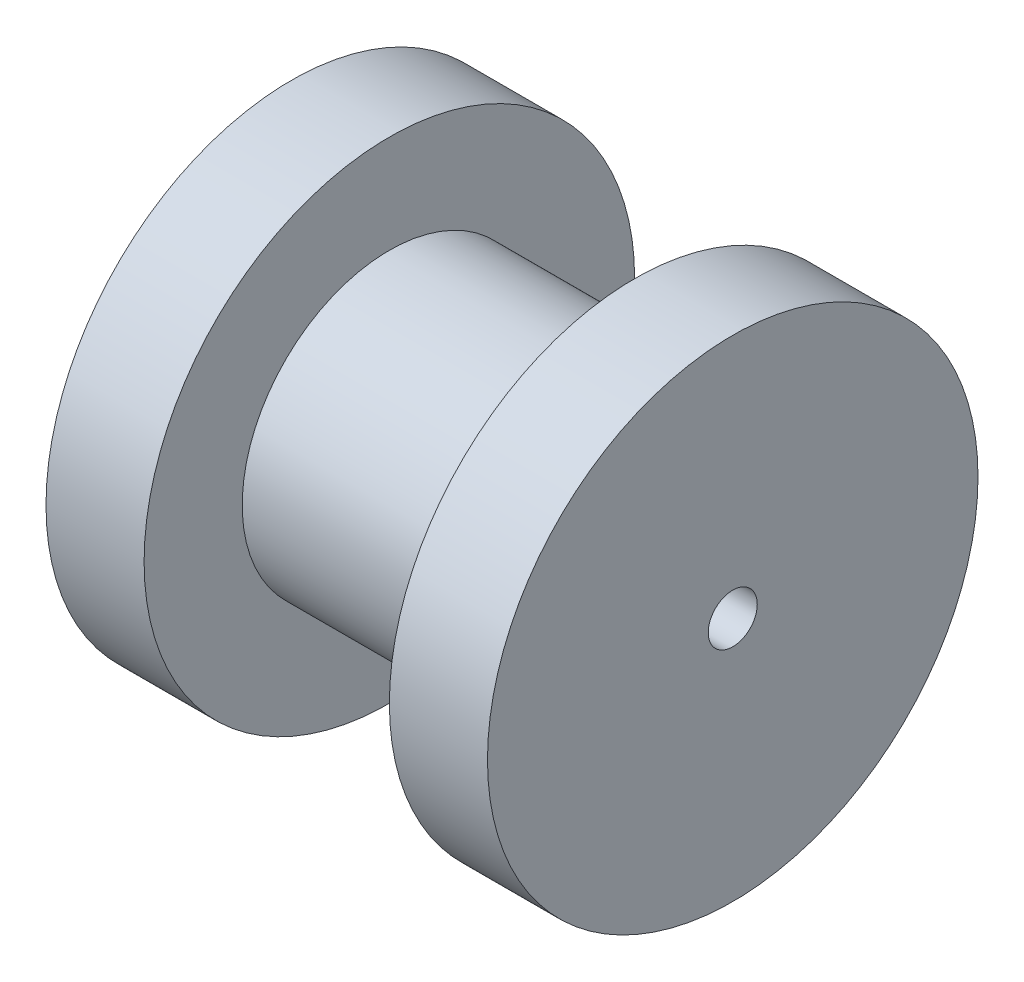
SolidWorks part; units mm, degrees
ref_plane "Front Plane" through (0, 0, 0) normal (0, 0, 1) x (1, 0, 0)
ref_plane "Top Plane" through (0, 0, 0) normal (0, 1, 0) x (1, 0, 0)
ref_plane "Right Plane" through (0, 0, 0) normal (1, 0, 0) x (0, 0, -1)
sketch "Sketch1" plane through (0, 0, 0) normal (1, 0, 0) x (0, 0, -1)
  circle A0 centre (0, 0) radius 5
extrude "Boss-Extrude1" add sketch "Sketch1" along normal blind 2
sketch "Sketch2" plane through (2, 0, 0) normal (1, 0, 0) x (0, 0, -1)
  circle A0 centre (0, 0) radius 3
extrude "Boss-Extrude2" add sketch "Sketch2" along normal blind 5
sketch "Sketch5" plane through (7, 0, 0) normal (1, 0, 0) x (0, 0, -1)
  circle A0 centre (0, 0) radius 5
extrude "Boss-Extrude4" add sketch "Sketch5" along normal blind 2
sketch "Sketch6" plane through (0, 0, 0) normal (-1, 0, 0) x (0, 0, 1)
  line L0 (0, 0) -> (0, 2.2) construction
  line L1 (0.096, 2.1979) -> (0.109, 2.4976)
  line L2 (-0.096, 2.1979) -> (-0.109, 2.4976)
  line L3 (0.4762, 2.1479) -> (0.5411, 2.4407)
  line L4 (0.2872, 2.1812) -> (0.3263, 2.4786)
  line L5 (0.8419, 2.0325) -> (0.9567, 2.3097)
  line L6 (0.6616, 2.0982) -> (0.7518, 2.3843)
  line L7 (1.1821, 1.8555) -> (1.3432, 2.1085)
  line L8 (1.0158, 1.9514) -> (1.1544, 2.2175)
  line L9 (1.4863, 1.622) -> (1.689, 1.8432)
  line L10 (1.3393, 1.7454) -> (1.5219, 1.9834)
  line L11 (1.7454, 1.3393) -> (1.9834, 1.5219)
  line L12 (1.622, 1.4863) -> (1.8432, 1.689)
  line L13 (1.9514, 1.0158) -> (2.2175, 1.1544)
  line L14 (1.8555, 1.1821) -> (2.1085, 1.3432)
  line L15 (2.0982, 0.6616) -> (2.3843, 0.7518)
  line L16 (2.0325, 0.8419) -> (2.3097, 0.9567)
  line L17 (2.1812, 0.2872) -> (2.4786, 0.3263)
  line L18 (2.1479, 0.4762) -> (2.4407, 0.5411)
  line L19 (2.1979, -0.096) -> (2.4976, -0.109)
  line L20 (2.1979, 0.096) -> (2.4976, 0.109)
  line L21 (2.1479, -0.4762) -> (2.4407, -0.5411)
  line L22 (2.1812, -0.2872) -> (2.4786, -0.3263)
  line L23 (2.0325, -0.8419) -> (2.3097, -0.9567)
  line L24 (2.0982, -0.6616) -> (2.3843, -0.7518)
  line L25 (1.8555, -1.1821) -> (2.1085, -1.3432)
  line L26 (1.9514, -1.0158) -> (2.2175, -1.1544)
  line L27 (1.622, -1.4863) -> (1.8432, -1.689)
  line L28 (1.7454, -1.3393) -> (1.9834, -1.5219)
  line L29 (1.3393, -1.7454) -> (1.5219, -1.9834)
  line L30 (1.4863, -1.622) -> (1.689, -1.8432)
  line L31 (1.0158, -1.9514) -> (1.1544, -2.2175)
  line L32 (1.1821, -1.8555) -> (1.3432, -2.1085)
  line L33 (0.6616, -2.0982) -> (0.7518, -2.3843)
  line L34 (0.8419, -2.0325) -> (0.9567, -2.3097)
  line L35 (0.2872, -2.1812) -> (0.3263, -2.4786)
  line L36 (0.4762, -2.1479) -> (0.5411, -2.4407)
  line L37 (-0.096, -2.1979) -> (-0.109, -2.4976)
  line L38 (0.096, -2.1979) -> (0.109, -2.4976)
  line L39 (-0.4762, -2.1479) -> (-0.5411, -2.4407)
  line L40 (-0.2872, -2.1812) -> (-0.3263, -2.4786)
  line L41 (-0.8419, -2.0325) -> (-0.9567, -2.3097)
  line L42 (-0.6616, -2.0982) -> (-0.7518, -2.3843)
  line L43 (-1.1821, -1.8555) -> (-1.3432, -2.1085)
  line L44 (-1.0158, -1.9514) -> (-1.1544, -2.2175)
  line L45 (-1.4863, -1.622) -> (-1.689, -1.8432)
  line L46 (-1.3393, -1.7454) -> (-1.5219, -1.9834)
  line L47 (-1.7454, -1.3393) -> (-1.9834, -1.5219)
  line L48 (-1.622, -1.4863) -> (-1.8432, -1.689)
  line L49 (-1.9514, -1.0158) -> (-2.2175, -1.1544)
  line L50 (-1.8555, -1.1821) -> (-2.1085, -1.3432)
  line L51 (-2.0982, -0.6616) -> (-2.3843, -0.7518)
  line L52 (-2.0325, -0.8419) -> (-2.3097, -0.9567)
  line L53 (-2.1812, -0.2872) -> (-2.4786, -0.3263)
  line L54 (-2.1479, -0.4762) -> (-2.4407, -0.5411)
  line L55 (-2.1979, 0.096) -> (-2.4976, 0.109)
  line L56 (-2.1979, -0.096) -> (-2.4976, -0.109)
  line L57 (-2.1479, 0.4762) -> (-2.4407, 0.5411)
  line L58 (-2.1812, 0.2872) -> (-2.4786, 0.3263)
  line L59 (-2.0325, 0.8419) -> (-2.3097, 0.9567)
  line L60 (-2.0982, 0.6616) -> (-2.3843, 0.7518)
  line L61 (-1.8555, 1.1821) -> (-2.1085, 1.3432)
  line L62 (-1.9514, 1.0158) -> (-2.2175, 1.1544)
  line L63 (-1.622, 1.4863) -> (-1.8432, 1.689)
  line L64 (-1.7454, 1.3393) -> (-1.9834, 1.5219)
  line L65 (-1.3393, 1.7454) -> (-1.5219, 1.9834)
  line L66 (-1.4863, 1.622) -> (-1.689, 1.8432)
  line L67 (-1.0158, 1.9514) -> (-1.1544, 2.2175)
  line L68 (-1.1821, 1.8555) -> (-1.3432, 2.1085)
  line L69 (-0.6616, 2.0982) -> (-0.7518, 2.3843)
  line L70 (-0.8419, 2.0325) -> (-0.9567, 2.3097)
  line L71 (-0.2872, 2.1812) -> (-0.3263, 2.4786)
  line L72 (-0.4762, 2.1479) -> (-0.5411, 2.4407)
  arc A0 (0.096, 2.1979) -> (-0.096, 2.1979) centre (0, 0) ccw
  arc A1 (-0.109, 2.4976) -> (-0.3263, 2.4786) centre (0, 0) ccw
  arc A2 (0.4762, 2.1479) -> (0.2872, 2.1812) centre (0, 0) ccw
  arc A3 (0.3263, 2.4786) -> (0.109, 2.4976) centre (0, 0) ccw
  arc A4 (0.8419, 2.0325) -> (0.6616, 2.0982) centre (0, 0) ccw
  arc A5 (0.7518, 2.3843) -> (0.5411, 2.4407) centre (0, 0) ccw
  arc A6 (1.1821, 1.8555) -> (1.0158, 1.9514) centre (0, 0) ccw
  arc A7 (1.1544, 2.2175) -> (0.9567, 2.3097) centre (0, 0) ccw
  arc A8 (1.4863, 1.622) -> (1.3393, 1.7454) centre (0, 0) ccw
  arc A9 (1.5219, 1.9834) -> (1.3432, 2.1085) centre (0, 0) ccw
  arc A10 (1.7454, 1.3393) -> (1.622, 1.4863) centre (0, 0) ccw
  arc A11 (1.8432, 1.689) -> (1.689, 1.8432) centre (0, 0) ccw
  arc A12 (1.9514, 1.0158) -> (1.8555, 1.1821) centre (0, 0) ccw
  arc A13 (2.1085, 1.3432) -> (1.9834, 1.5219) centre (0, 0) ccw
  arc A14 (2.0982, 0.6616) -> (2.0325, 0.8419) centre (0, 0) ccw
  arc A15 (2.3097, 0.9567) -> (2.2175, 1.1544) centre (0, 0) ccw
  arc A16 (2.1812, 0.2872) -> (2.1479, 0.4762) centre (0, 0) ccw
  arc A17 (2.4407, 0.5411) -> (2.3843, 0.7518) centre (0, 0) ccw
  arc A18 (2.1979, -0.096) -> (2.1979, 0.096) centre (0, 0) ccw
  arc A19 (2.4976, 0.109) -> (2.4786, 0.3263) centre (0, 0) ccw
  arc A20 (2.1479, -0.4762) -> (2.1812, -0.2872) centre (0, 0) ccw
  arc A21 (2.4786, -0.3263) -> (2.4976, -0.109) centre (0, 0) ccw
  arc A22 (2.0325, -0.8419) -> (2.0982, -0.6616) centre (0, 0) ccw
  arc A23 (2.3843, -0.7518) -> (2.4407, -0.5411) centre (0, 0) ccw
  arc A24 (1.8555, -1.1821) -> (1.9514, -1.0158) centre (0, 0) ccw
  arc A25 (2.2175, -1.1544) -> (2.3097, -0.9567) centre (0, 0) ccw
  arc A26 (1.622, -1.4863) -> (1.7454, -1.3393) centre (0, 0) ccw
  arc A27 (1.9834, -1.5219) -> (2.1085, -1.3432) centre (0, 0) ccw
  arc A28 (1.3393, -1.7454) -> (1.4863, -1.622) centre (0, 0) ccw
  arc A29 (1.689, -1.8432) -> (1.8432, -1.689) centre (0, 0) ccw
  arc A30 (1.0158, -1.9514) -> (1.1821, -1.8555) centre (0, 0) ccw
  arc A31 (1.3432, -2.1085) -> (1.5219, -1.9834) centre (0, 0) ccw
  arc A32 (0.6616, -2.0982) -> (0.8419, -2.0325) centre (0, 0) ccw
  arc A33 (0.9567, -2.3097) -> (1.1544, -2.2175) centre (0, 0) ccw
  arc A34 (0.2872, -2.1812) -> (0.4762, -2.1479) centre (0, 0) ccw
  arc A35 (0.5411, -2.4407) -> (0.7518, -2.3843) centre (0, 0) ccw
  arc A36 (-0.096, -2.1979) -> (0.096, -2.1979) centre (0, 0) ccw
  arc A37 (0.109, -2.4976) -> (0.3263, -2.4786) centre (0, 0) ccw
  arc A38 (-0.4762, -2.1479) -> (-0.2872, -2.1812) centre (0, 0) ccw
  arc A39 (-0.3263, -2.4786) -> (-0.109, -2.4976) centre (0, 0) ccw
  arc A40 (-0.8419, -2.0325) -> (-0.6616, -2.0982) centre (0, 0) ccw
  arc A41 (-0.7518, -2.3843) -> (-0.5411, -2.4407) centre (0, 0) ccw
  arc A42 (-1.1821, -1.8555) -> (-1.0158, -1.9514) centre (0, 0) ccw
  arc A43 (-1.1544, -2.2175) -> (-0.9567, -2.3097) centre (0, 0) ccw
  arc A44 (-1.4863, -1.622) -> (-1.3393, -1.7454) centre (0, 0) ccw
  arc A45 (-1.5219, -1.9834) -> (-1.3432, -2.1085) centre (0, 0) ccw
  arc A46 (-1.7454, -1.3393) -> (-1.622, -1.4863) centre (0, 0) ccw
  arc A47 (-1.8432, -1.689) -> (-1.689, -1.8432) centre (0, 0) ccw
  arc A48 (-1.9514, -1.0158) -> (-1.8555, -1.1821) centre (0, 0) ccw
  arc A49 (-2.1085, -1.3432) -> (-1.9834, -1.5219) centre (0, 0) ccw
  arc A50 (-2.0982, -0.6616) -> (-2.0325, -0.8419) centre (0, 0) ccw
  arc A51 (-2.3097, -0.9567) -> (-2.2175, -1.1544) centre (0, 0) ccw
  arc A52 (-2.1812, -0.2872) -> (-2.1479, -0.4762) centre (0, 0) ccw
  arc A53 (-2.4407, -0.5411) -> (-2.3843, -0.7518) centre (0, 0) ccw
  arc A54 (-2.1979, 0.096) -> (-2.1979, -0.096) centre (0, 0) ccw
  arc A55 (-2.4976, -0.109) -> (-2.4786, -0.3263) centre (0, 0) ccw
  arc A56 (-2.1479, 0.4762) -> (-2.1812, 0.2872) centre (0, 0) ccw
  arc A57 (-2.4786, 0.3263) -> (-2.4976, 0.109) centre (0, 0) ccw
  arc A58 (-2.0325, 0.8419) -> (-2.0982, 0.6616) centre (0, 0) ccw
  arc A59 (-2.3843, 0.7518) -> (-2.4407, 0.5411) centre (0, 0) ccw
  arc A60 (-1.8555, 1.1821) -> (-1.9514, 1.0158) centre (0, 0) ccw
  arc A61 (-2.2175, 1.1544) -> (-2.3097, 0.9567) centre (0, 0) ccw
  arc A62 (-1.622, 1.4863) -> (-1.7454, 1.3393) centre (0, 0) ccw
  arc A63 (-1.9834, 1.5219) -> (-2.1085, 1.3432) centre (0, 0) ccw
  arc A64 (-1.3393, 1.7454) -> (-1.4863, 1.622) centre (0, 0) ccw
  arc A65 (-1.689, 1.8432) -> (-1.8432, 1.689) centre (0, 0) ccw
  arc A66 (-1.0158, 1.9514) -> (-1.1821, 1.8555) centre (0, 0) ccw
  arc A67 (-1.3432, 2.1085) -> (-1.5219, 1.9834) centre (0, 0) ccw
  arc A68 (-0.6616, 2.0982) -> (-0.8419, 2.0325) centre (0, 0) ccw
  arc A69 (-0.9567, 2.3097) -> (-1.1544, 2.2175) centre (0, 0) ccw
  arc A70 (-0.2872, 2.1812) -> (-0.4762, 2.1479) centre (0, 0) ccw
  arc A71 (-0.5411, 2.4407) -> (-0.7518, 2.3843) centre (0, 0) ccw
  point P186 (0, 0)
  dimension "D1" = 36
extrude "Cut-Extrude1" cut sketch "Sketch6" against normal blind 1
sketch "Sketch7" plane through (9, 0, 0) normal (1, 0, 0) x (0, 0, -1)
  circle A0 centre (0, 0) radius 0.5
extrude "Cut-Extrude2" cut sketch "Sketch7" against normal through all
